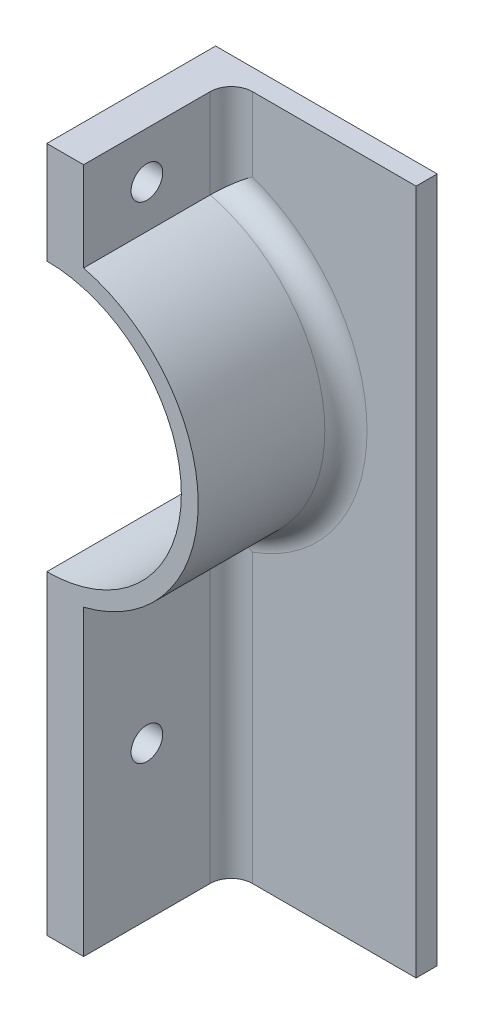
SolidWorks part; units mm, degrees
ref_plane "Front Plane" through (0, 0, 0) normal (0, 0, 1) x (1, 0, 0)
ref_plane "Top Plane" through (0, 0, 0) normal (0, 1, 0) x (1, 0, 0)
ref_plane "Right Plane" through (0, 0, 0) normal (1, 0, 0) x (0, 0, -1)
sketch "Sketch2" plane through (0, 0, 0) normal (0, 0, 1) x (1, 0, 0)
  line L0 (0, 0) -> (0, 82.55)
  line L1 (0, 82.55) -> (50.8, 82.55)
  line L2 (50.8, 82.55) -> (50.8, 0)
  line L3 (50.8, 0) -> (0, 0)
  line L4 (24.13, 82.55) -> (24.13, 0)
  line L7 (19.7022, 82.55) -> (19.7022, 71.7804)
  line L8 (19.7022, 0) -> (19.7022, 36.4236)
  line L9 (28.5578, 82.55) -> (28.5578, 71.7804)
  line L10 (28.5578, 0) -> (28.5578, 36.4236)
  circle A0 centre (24.13, 54.102) radius 16.1925
  arc A1 (19.7022, 71.7804) -> (19.7022, 36.4236) centre (24.13, 54.102) ccw
  arc A2 (28.5578, 36.4236) -> (28.5578, 71.7804) centre (24.13, 54.102) ccw
sketch "Sketch3" plane through (0, 0, 0) normal (1, 0, 0) x (0, 0, -1)
  circle A0 centre (-12.7, 18.4309) radius 1.905
  circle A1 centre (-12.7, 76.9461) radius 1.905
extrude "Boss-Extrude3" add sketch "Sketch2" along normal blind 20.32 contours L10 A2 L9 L1 L4 A0 L3 region at (24.9754, 18.9547, 0)
extrude "Boss-Extrude4" add sketch "Sketch2<5>" along normal blind 2.54 contours A2 L10 L3 L2 L1 L9 region at (40.9977, 38.1258, 0)
sketch "Sketch2<5>" plane through (0, 0, 0) normal (0, 0, 1) x (1, 0, 0) same geometry as "Sketch2"
fillet "Fillet2" radius 2.54 3 edges at (28.5578, 18.2118, 2.54) (28.5578, 77.1652, 2.54) (42.3545, 54.102, 2.54)
extrude "Cut-Extrude2" cut sketch "Sketch3" along normal through all both
